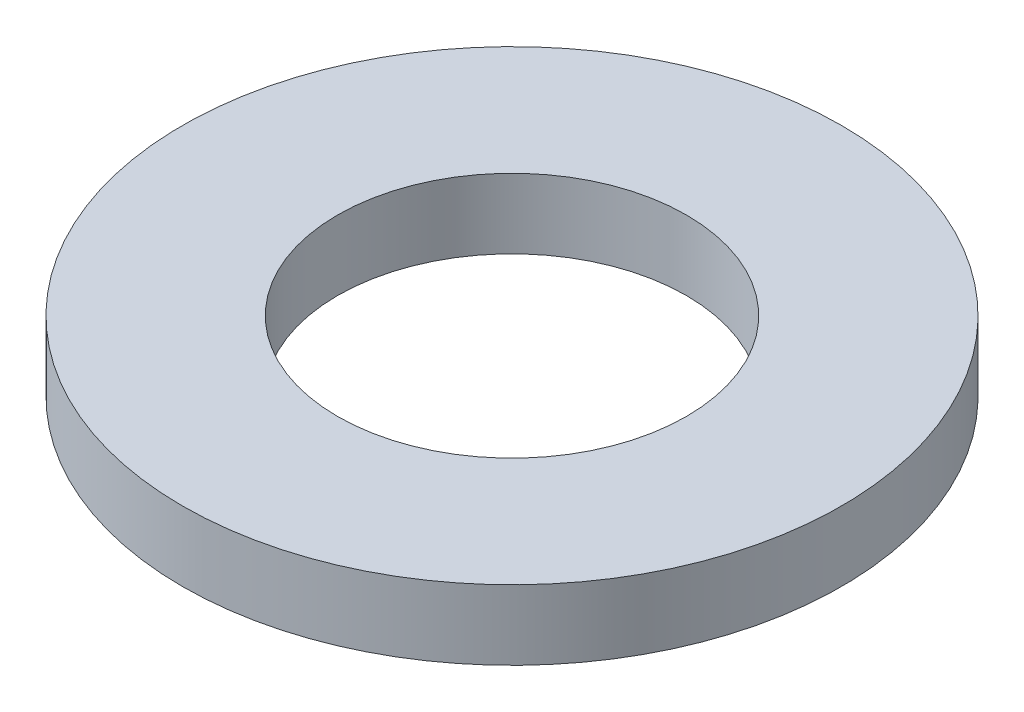
SolidWorks part; units mm, degrees
ref_plane "Front Plane" through (0, 0, 0) normal (0, 0, 1) x (1, 0, 0)
ref_plane "Top Plane" through (0, 0, 0) normal (0, 1, 0) x (1, 0, 0)
ref_plane "Right Plane" through (0, 0, 0) normal (1, 0, 0) x (0, 0, -1)
sketch "Sketch1" plane through (0, 0, 0) normal (0, 1, 0) x (1, 0, 0)
  circle A0 centre (0, 0) radius 85
  dimension "FLANGE_OD" = 170
extrude "Boss-Extrude1" add sketch "Sketch1" along normal blind 18
sketch "Sketch2" plane through (0, 0, 0) normal (0, 1, 0) x (1, 0, 0)
  circle A0 centre (0, 0) radius 45
  dimension "BORE_D" = 90
extrude "Cut-Extrude1" cut sketch "Sketch2" along normal through all
sketch "Sketch3" plane through (0, 18, 0) normal (0, 1, 0) x (1, 0, 0)
  circle A0 centre (0, 0) radius 26.5108 construction
  circle A1 centre (-26.5108, 0) radius 4.0987
  dimension "BOLT_D" = 8.1974
  dimension "BOLT_PCD" = 53.0217
extrude "Cut-Extrude2" cut sketch "Sketch3" against normal blind 13.4543 rebuild error yes
pattern_circular "CirPattern1" count 5 over 360 rebuild error yes
